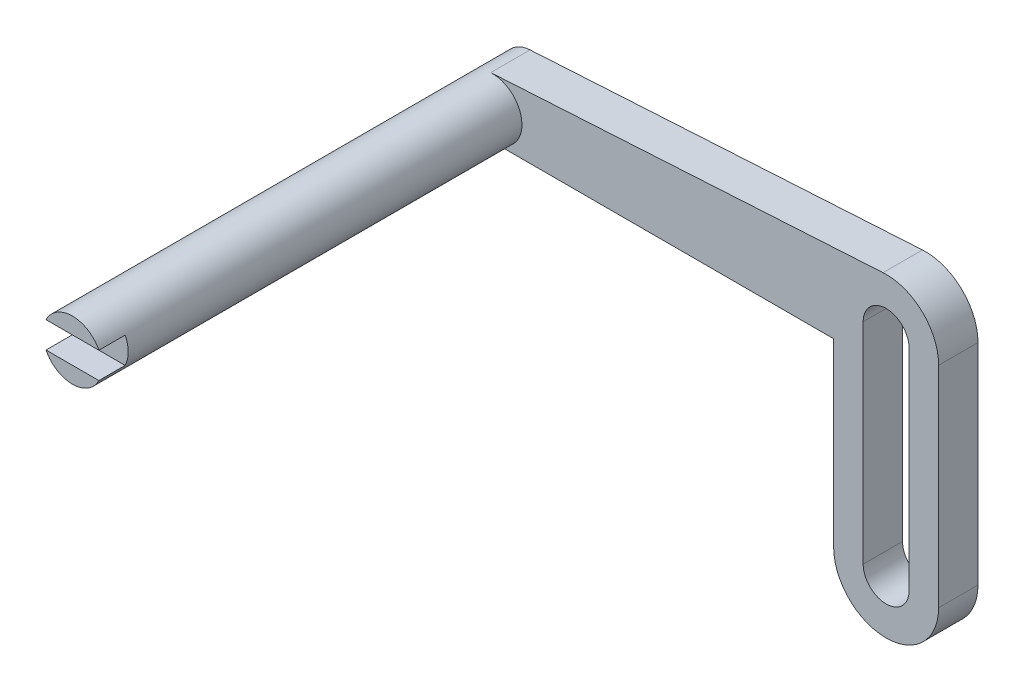
SolidWorks part; units mm, degrees
ref_plane "前视基准面" through (0, 0, 0) normal (0, 0, 1) x (1, 0, 0)
ref_plane "上视基准面" through (0, 0, 0) normal (0, 1, 0) x (1, 0, 0)
ref_plane "右视基准面" through (0, 0, 0) normal (1, 0, 0) x (0, 0, -1)
sketch "草图1" plane through (0, 0, 0) normal (0, 0, 1) x (1, 0, 0)
  line L0 (0, -2.25) -> (26, -2.25)
  line L1 (0, 0) -> (30, 0) construction
  line L2 (-0.1313, 2.2462) -> (29.7667, 3.9932)
  line L3 (34, 0) -> (34, -20)
  line L4 (34, -20) -> (26, -20)
  line L5 (26, -20) -> (26, -2.25)
  line L6 (31.75, -16) -> (31.75, 0)
  line L7 (28.25, 0) -> (28.25, -16)
  line L8 (30, 0) -> (30, -16) construction
  circle A0 centre (0, 0) radius 2.25
  circle A2 centre (30, 0) radius 4
  circle A3 centre (30, 0) radius 1.75
  circle A4 centre (30, -16) radius 1.75
  dimension "D1" = 4.5
  dimension "D5" = 8
  dimension "D6" = 3.5
  dimension "D7" = 3.5
  dimension "D2" = 30
  dimension "D3" = 8
  dimension "D4" = 20
  dimension "D8" = 16
extrude "凸台-拉伸1" add sketch "草图1" along normal blind 3 contours A0 | A0 L1 | L1 A0 | A2 region at (1.886, -1.886, 0) region at (0, 0, 0) region at (32.669, 2.8295, 0)
extrude "凸台-拉伸2" add sketch "草图1<3>" along normal blind 35 contours A0 region at (0, 0, 0)
sketch "草图1<3>" plane through (0, 0, 0) normal (0, 0, 1) x (1, 0, 0) same geometry as "草图1"
sketch "草图2" plane through (0, 0, 35) normal (0, 0, 1) x (1, 0, 0)
  line L1 (2.5, 1) -> (-2.5, 1)
  line L2 (2.5, 1) -> (2.5, -1)
  line L3 (2.5, -1) -> (-2.5, -1)
  line L4 (-2.5, 1) -> (-2.5, -1)
  line L5 (2.5, 1) -> (-2.5, -1) construction
  line L6 (2.5, -1) -> (-2.5, 1) construction
  point P0 (0, 0)
  dimension "D1" = 2
  dimension "D2" = 5
extrude "切除-拉伸1" cut sketch "草图2" against normal blind 2
fillet "圆角1" radius 4 2 edges at (26, -20, 1.5) (34, -20, 1.5)
